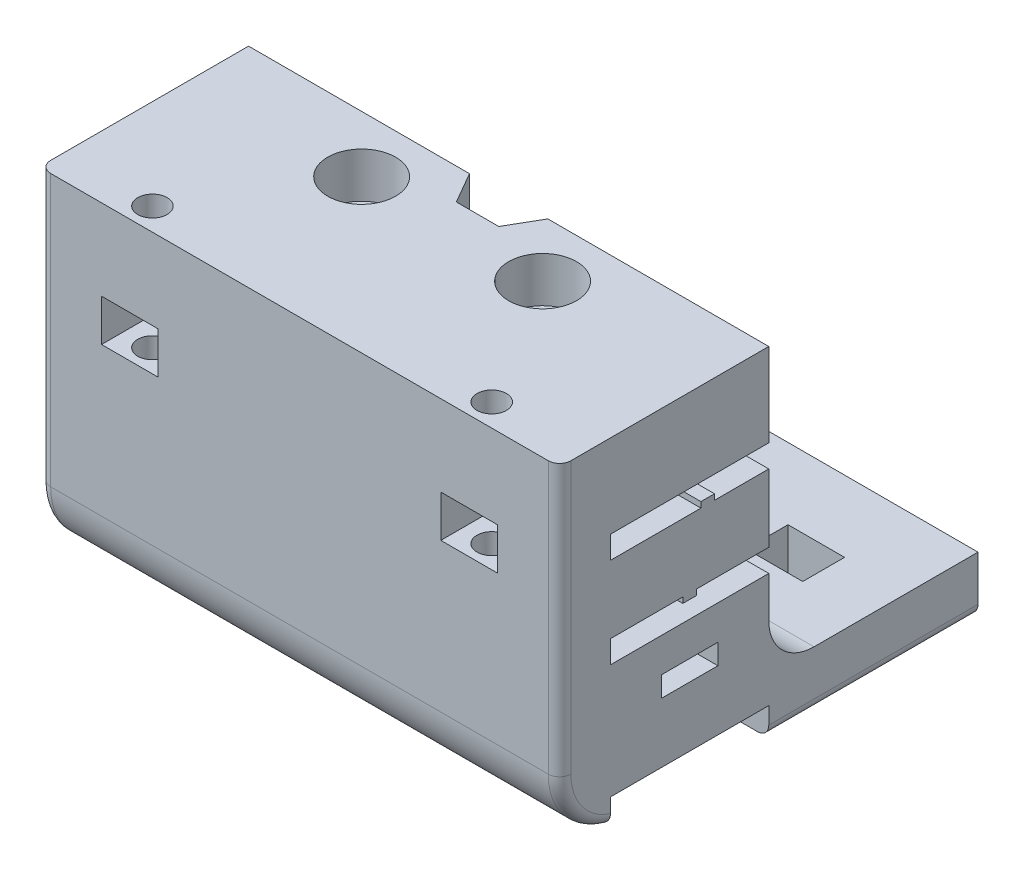
SolidWorks part; units mm, degrees
material "1060 Сплав"
ref_plane "Front" through (0, 0, 0) normal (0, 0, 1) x (1, 0, 0)
ref_plane "Top" through (0, 0, 0) normal (0, 1, 0) x (1, 0, 0)
ref_plane "Right" through (0, 0, 0) normal (1, 0, 0) x (0, 0, -1)
sketch "Эскиз1" plane through (0, 0, 0) normal (0, 0, 1) x (1, 0, 0)
  line L1 (-23, -15) -> (23, -15)
  line L2 (-23, -15) -> (-23, 15)
  line L3 (-23, 15) -> (23, 15)
  line L4 (23, -15) -> (23, 15)
  line L5 (-23, -15) -> (23, 15) construction
  line L6 (-23, 15) -> (23, -15) construction
  point P0 (0, 0)
  dimension "D1" = 30
  dimension "D2" = 46
extrude "Бобышка-Вытянуть1" add sketch "Эскиз1" along normal blind 3.5
sketch "Эскиз2" plane through (0, 0, 0) normal (0, 0, -1) x (-1, 0, 0)
  line L0 (23, 15) -> (23, -15) construction
  line L1 (-23, -15) -> (23, -15)
  line L2 (-23, -15) -> (-23, -10)
  line L3 (-23, -10) -> (23, -10)
  line L4 (23, -15) -> (23, -10)
  dimension "D1" = 5
extrude "Бобышка-Вытянуть2" add sketch "Эскиз2" along normal blind 33.5
sketch "Эскиз4" plane through (0, 15, 0) normal (0, 1, 0) x (1, 0, 0)
  line L0 (15, -1.5) -> (-15, -1.5) construction
  line L3 (0, -1.5) -> (0, -3.5) construction
  line L4 (23, -3.5) -> (-23, -3.5) construction
  circle A0 centre (15, -1.5) radius 1.3
  circle A1 centre (-15, -1.5) radius 1.3
  dimension "D1" = 2
extrude "Вырез-Вытянуть2" cut sketch "Эскиз4" against normal blind 15
sketch "Эскиз5" plane through (0, 0, -33.5) normal (0, 0, -1) x (-1, 0, 0)
  line L0 (-23, -12.5) -> (23, -12.5) construction
  line L1 (-23, -10) -> (-23, -15) construction
  line L2 (23, -15) -> (23, -10) construction
  circle A0 centre (-20, -12.5) radius 1.3
  circle A1 centre (20, -12.5) radius 1.3
  point P10 (0, -12.5)
  dimension "D1" = 20
  dimension "D2" = 20
extrude "Вырез-Вытянуть3" cut sketch "Эскиз5" against normal blind 15
sketch "Эскиз6" plane through (0, -10, 0) normal (0, 1, 0) x (1, 0, 0)
  line L0 (-23, 23.5) -> (23, 23.5) construction
  line L1 (-23, 33.5) -> (-23, 0) construction
  line L2 (23, 33.5) -> (23, 0) construction
  line L3 (-23, 33.5) -> (23, 33.5) construction
  line L5 (-17.5, 23.5) -> (-12.5, 23.5)
  line L6 (-17.5, 23.5) -> (-17.5, 27.2)
  line L7 (-17.5, 27.2) -> (-12.5, 27.2)
  line L8 (-12.5, 23.5) -> (-12.5, 27.2)
  line L9 (12.5, 23.5) -> (17.5, 23.5)
  line L10 (12.5, 23.5) -> (12.5, 27.2)
  line L11 (12.5, 27.2) -> (17.5, 27.2)
  line L12 (17.5, 23.5) -> (17.5, 27.2)
  point P16 (0, 23.5)
  dimension "D1" = 10
  dimension "D2" = 3.7
  dimension "D3" = 5
  dimension "D4" = 3.7
  dimension "D5" = 5
  dimension "D6" = 12.5
  dimension "D7" = 12.5
extrude "Вырез-Вытянуть4" cut sketch "Эскиз6" against normal up to next
sketch "Эскиз7" plane through (0, 0, 0) normal (0, 0, -1) x (-1, 0, 0)
  line L1 (23, 15) -> (-23, 15)
  line L2 (23, 15) -> (23, -10)
  line L3 (23, -10) -> (-23, -10)
  line L4 (-23, 15) -> (-23, -10)
extrude "Бобышка-Вытянуть3" add sketch "Эскиз7" along normal blind 15
sketch "Эскиз8" plane through (0, 0, -15) normal (0, 0, -1) x (-1, 0, 0)
  line L0 (-23, 7.62) -> (23, 7.62)
  line L1 (23, -10) -> (23, 15) construction
  line L2 (-23, 15) -> (-23, -10) construction
  line L3 (-23, 5.62) -> (-23, 7.62)
  line L5 (23, 5.62) -> (-23, 5.62)
  line L6 (-23, -2.38) -> (-23, -0.38)
  line L7 (23, 5.62) -> (23, 7.62)
  line L8 (23, -2.38) -> (-23, -2.38)
  line L9 (23, -2.38) -> (23, -0.38)
  line L10 (-23, -0.38) -> (23, -0.38)
  dimension "D2" = 2
extrude "Вырез-Вытянуть5" cut sketch "Эскиз8" against normal blind 14
sketch "Эскиз10" plane through (0, 0, 3.5) normal (0, 0, 1) x (1, 0, 0)
  line L0 (0, 15) -> (0, -15) construction
  line L1 (23, 15) -> (-23, 15) construction
  line L2 (-23, -15) -> (23, -15) construction
  line L3 (0, 6) -> (15, 6) construction
  line L4 (-17.5, 7.85) -> (-12.5, 4.15) construction
  line L5 (17.5, 4.15) -> (12.5, 4.15)
  line L6 (17.5, 4.15) -> (17.5, 7.85)
  line L7 (17.5, 7.85) -> (12.5, 7.85)
  line L8 (12.5, 4.15) -> (12.5, 7.85)
  line L9 (17.5, 4.15) -> (12.5, 7.85) construction
  line L10 (17.5, 7.85) -> (12.5, 4.15) construction
  line L11 (-17.5, 4.15) -> (-12.5, 7.85) construction
  line L12 (-12.5, 4.15) -> (-12.5, 7.85)
  line L13 (-17.5, 7.85) -> (-12.5, 7.85)
  line L14 (-17.5, 4.15) -> (-17.5, 7.85)
  line L15 (-17.5, 4.15) -> (-12.5, 4.15)
  dimension "D1" = 15
  dimension "D2" = 5
  dimension "D3" = 3.7
  dimension "D4" = 9
extrude "Вырез-Вытянуть7" cut sketch "Эскиз10" against normal blind 5
fillet "Скругление1" radius 6 1 edges at (0, -15, 3.5)
fillet "Скругление2" radius 4 1 edges at (0, -10, -15)
sketch "Эскиз11" plane through (0, 0, -15) normal (0, 0, -1) x (-1, 0, 0)
  line L0 (-23, 5.62) -> (23, 5.62) construction
  line L1 (-2.5, 5.62) -> (2.5, 5.62)
  line L2 (-2.5, 5.62) -> (-2.5, -17.5157)
  line L3 (-2.5, -17.5157) -> (2.5, -17.5157)
  line L4 (2.5, 5.62) -> (2.5, -17.5157)
  line L5 (-23, 5.62) -> (-17.5, 5.62) construction
  point P0 (0, 5.62)
  dimension "D1" = 2.5
  dimension "D2" = 2.5
extrude "Вырез-Вытянуть8" cut sketch "Эскиз11" against normal blind 14
fillet "Скругление3" radius 4 4 edges at (-2.5, -2.38, -8) (-2.5, 5.62, -8) (2.5, 5.62, -8) (2.5, -2.38, -8)
fillet "Скругление4" radius 1 6 edges at (23, -15, -18) (23, -13.2426, 1.7426) (-23, -15, -18) (-23, -13.2426, 1.7426) (23, 3, 3.5) (-23, 3, 3.5)
sketch "Эскиз12" plane through (23, 0, 0) normal (1, 0, 0) x (0, 0, -1)
  line L0 (1, 5.62) -> (9, 5.62) construction
  line L1 (1, 5.62) -> (15, 5.62) construction
  line L2 (15, 5.62) -> (10.2, 5.62) construction
  line L3 (1, -0.38) -> (15, -0.38) construction
  line L4 (9, 6.12) -> (10.2, 6.12)
  line L5 (9, 6.12) -> (9, 5.62)
  line L6 (7.4, -0.88) -> (8.6, -0.88)
  line L7 (10.2, 6.12) -> (10.2, 5.62)
  line L8 (9, 5.62) -> (10.2, 5.62)
  line L9 (8.6, -0.38) -> (7.4, -0.38)
  line L10 (7.4, -0.38) -> (7.4, -0.88)
  line L11 (8.6, -0.38) -> (8.6, -0.88)
  line L12 (15, 5.62) -> (15, -0.38) construction
  point P16 (0, 0)
  point P17 (0, 0)
  point P19 (8.6, -0.63)
  dimension "D1" = 4.8
  dimension "D2" = 1.2
  dimension "D3" = 0.5
  dimension "D4" = 0.5
  dimension "D5" = 6.4
extrude "Бобышка-Вытянуть4" add sketch "Эскиз12" against normal blind 10
sketch "Эскиз13" plane through (-23, 0, 0) normal (-1, 0, 0) x (0, 0, 1)
  line L0 (-8.6, 5.62) -> (-7.4, 5.62)
  line L1 (-8.6, 6.12) -> (-7.4, 6.12)
  line L2 (-8.6, 6.12) -> (-8.6, 5.62)
  line L3 (-10.2, -0.88) -> (-9, -0.88)
  line L4 (-7.4, 6.12) -> (-7.4, 5.62)
  line L6 (-10.2, -0.38) -> (-9, -0.38)
  line L8 (-10.2, -0.38) -> (-10.2, -0.88)
  line L9 (-9, -0.38) -> (-9, -0.88)
  line L11 (-15, -0.38) -> (-15, 5.62) construction
  dimension "D1" = 1.2
  dimension "D2" = 4.8
  dimension "D3" = 1.2
extrude "Бобышка-Вытянуть5" add sketch "Эскиз13" against normal blind 10
sketch "Эскиз14" plane through (0, -15, 0) normal (0, -1, 0) x (1, 0, 0)
  line L1 (-28.5402, -1) -> (28.5402, -1)
  line L2 (-28.5402, -1) -> (-28.5402, -15)
  line L3 (-28.5402, -15) -> (28.5402, -15)
  line L4 (28.5402, -1) -> (28.5402, -15)
  line L5 (-28.5402, -1) -> (28.5402, -15) construction
  line L6 (-28.5402, -15) -> (28.5402, -1) construction
  point P0 (0, -8)
extrude "Вырез-Вытянуть9" cut sketch "Эскиз14" against normal blind 2.5
fillet "Скругление5" radius 4 2 edges at (2.5, -12.5, -8) (-2.5, -12.5, -8)
sketch "Эскиз15" plane through (0, -12.5, 0) normal (0, -1, 0) x (1, 0, 0)
  line L0 (-23, -8) -> (23, -8) construction
  line L1 (-23, -1) -> (-23, -15) construction
  line L2 (23, -15) -> (23, -1) construction
  circle A2 centre (-19, -8) radius 1.3
  circle A3 centre (19, -8) radius 1.3
  dimension "D1" = 4
  dimension "D2" = 4
extrude "Вырез-Вытянуть10" cut sketch "Эскиз15" against normal blind 8
sketch "Эскиз16" plane through (-23, 0, 0) normal (-1, 0, 0) x (0, 0, 1)
  line L0 (-8, -12.5) -> (-8, -6.3) construction
  line L1 (-10.5, -5.4) -> (-5.5, -5.4)
  line L2 (-10.5, -5.4) -> (-10.5, -7.2)
  line L3 (-10.5, -7.2) -> (-5.5, -7.2)
  line L4 (-5.5, -5.4) -> (-5.5, -7.2)
  line L5 (-10.5, -5.4) -> (-5.5, -7.2) construction
  line L6 (-10.5, -7.2) -> (-5.5, -5.4) construction
  line L7 (-1, -12.5) -> (-15, -12.5) construction
  point P0 (-8, -6.3)
  dimension "D1" = 5
  dimension "D2" = 1.8
  dimension "D3" = 6.2
extrude "Вырез-Вытянуть11" cut sketch "Эскиз16" against normal blind 7
sketch "Эскиз17" plane through (23, 0, 0) normal (1, 0, 0) x (0, 0, -1)
  line L0 (8, -12.5) -> (8, -6.3) construction
  line L1 (15, -12.5) -> (1, -12.5) construction
  line L3 (5.5, -5.4) -> (10.5, -5.4)
  line L4 (5.5, -5.4) -> (5.5, -7.2)
  line L5 (5.5, -7.2) -> (10.5, -7.2)
  line L6 (10.5, -5.4) -> (10.5, -7.2)
  line L7 (5.5, -5.4) -> (10.5, -7.2) construction
  line L8 (5.5, -7.2) -> (10.5, -5.4) construction
  dimension "D1" = 6.2
  dimension "D2" = 1.8
  dimension "D3" = 5
extrude "Вырез-Вытянуть12" cut sketch "Эскиз17" against normal blind 7
sketch "Эскиз18" plane through (0, 15, 0) normal (0, 1, 0) x (1, 0, 0)
  line L0 (23, -2.5) -> (23, 15) construction
  line L2 (22, -3.5) -> (-22, -3.5) construction
  line L3 (0, 10) -> (8, 10) construction
  line L5 (3.7528, 15.5) -> (1.8764, 18.75)
  line L6 (1.8764, 18.75) -> (-1.8764, 18.75)
  line L7 (-1.8764, 18.75) -> (-3.7528, 15.5)
  line L8 (-3.7528, 15.5) -> (-1.8764, 12.25)
  line L9 (-1.8764, 12.25) -> (1.8764, 12.25)
  line L10 (1.8764, 12.25) -> (3.7528, 15.5)
  circle A0 centre (8, 10) radius 3
  circle A1 centre (-8, 10) radius 3
  circle A2 centre (0, 15.5) radius 3.25 construction
  dimension "D2" = 13.5
  dimension "D1" = 8
  dimension "D3" = 19
  dimension "D4" = 23
extrude "Вырез-Вытянуть13" cut sketch "Эскиз18" against normal blind 4
